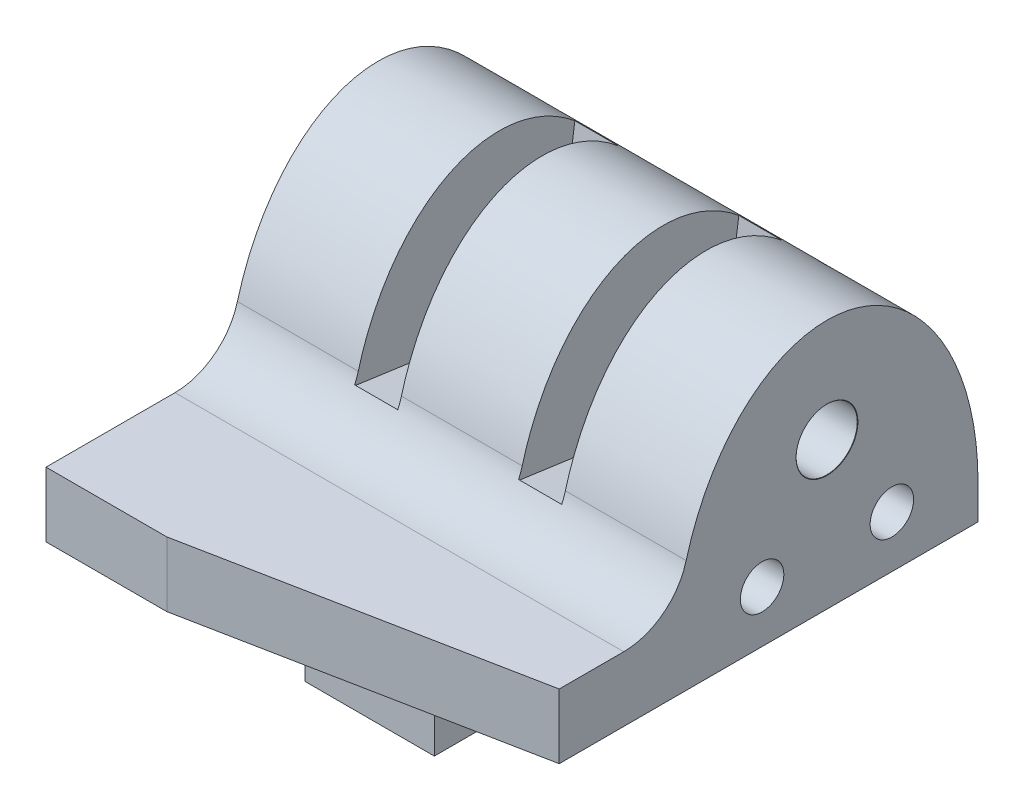
SolidWorks part; units mm, degrees
material "ABS"
ref_plane "Front Plane" through (0, 0, 0) normal (1, 0, 0) x (0, 1, 0)
ref_plane "Top Plane" through (0, 0, 0) normal (0, 0, 1) x (0, 1, 0)
ref_plane "Right Plane" through (0, 0, 0) normal (0, 1, 0) x (-1, 0, 0)
ref_plane "Plane1" through (8.89, 0, 0) normal (1, 0, 0) x (0, 1, 0)
sketch "Sketch1" plane through (0, 0, 0) normal (1, 0, 0) x (0, 1, 0)
  line L0 (0, 0) -> (0, 35.56)
  line L1 (0, 0) -> (-4.6261, 0) construction
  line L2 (0, 0) -> (2.54, 0)
  line L3 (0, 35.56) -> (4.7625, 35.56)
  line L4 (4.7625, 35.56) -> (4.7625, 26.0701)
  line L5 (2.54, 11.1125) -> (18.415, 11.1125) construction
  arc A0 (4.7625, 26.0701) -> (8.2778, 21.4738) centre (9.525, 26.0701) ccw
  ellipse E0 centre (2.54, 11.1125) end of major axis (-13.335, 11.1125) minor radius 11.1125 (2.54, 0) -> (8.2778, 21.4738) ccw
  point P12 (10.795, 11.1125)
  dimension "D3" = 22.225
  dimension "D4" = 4.7625
  dimension "D1" = 2.54
  dimension "D2" = 35.56
  dimension "D5" = 4.7625
  dimension "D6" = 31.75
  dimension "D7" = 7.62
extrude "Boss-Extrude1" add sketch "Sketch1" along normal blind 33.02
hole_wizard "M4 Clearance Hole1" positions "Sketch2" profile "Sketch3" hole size "M4" standard "ANSI Metric" end condition through all
sketch "Sketch2" plane through (33.02, 0, 0) normal (1, 0, 0) x (0, 0, -1)
  point P0 (-11.1125, 10.795)
sketch "Sketch3" plane through (33.02, 10.795, 11.1125) normal (0, 1, 0) x (0, 0, -1)
  line L0 (0, 0) -> (0, 33.02)
  line L1 (0, 33.02) -> (2.25, 33.02)
  line L2 (2.25, 33.02) -> (2.25, 0.021)
  line L3 (2.25, 0.021) -> (2.275, 0)
  line L5 (2.275, 0) -> (0, 0)
  line L6 (-2.25, 0.021) -> (-2.275, 0) construction
  line L11 (0, -6.35) -> (0, 107.95) construction
  dimension "Thru Hole Dia." = 4.5
  dimension "Thru Hole Depth" = 33.02
  dimension "Near C'Sink Dia." = 4.55
  dimension "Near C'Sink Angle" = 100
sketch "Sketch5" plane through (8.89, 0, 0) normal (-1, 0, 0) x (0, -1, 0)
  line L0 (0, 0) -> (0, 35.56) construction
  line L1 (0, 25.4) -> (9.525, 25.4)
  line L2 (0, 25.4) -> (0, 0)
  line L3 (0, 0) -> (9.525, 0)
  line L4 (9.525, 25.4) -> (9.525, 0)
  line L5 (4.7625, 19.05) -> (4.7625, 6.35)
  dimension "D1" = 12.7
  dimension "D2" = 4.7625
  dimension "D3" = 9.525
  dimension "D4" = 6.35
  dimension "D5" = 25.4
extrude "Boss-Extrude2" add sketch "Sketch5" against normal blind 9.525 contours L4 L1 L3 region at (8.89, -4.7625, 25.1287)
hole_wizard "#8 Clearance Hole1" positions "Sketch6" profile "Sketch7" hole size "#8" standard "ANSI Inch" end condition through all
sketch "Sketch6" plane through (0, 0, 0) normal (-1, 0, 0) x (0, 0, 1)
  point P0 (6.35, -4.7625)
  point P3 (19.05, -4.7625)
sketch "Sketch7" plane through (0, -4.7625, 6.35) normal (0, 1, 0) x (0, 0, 1)
  line L0 (0, 0) -> (0, 33.02)
  line L1 (0, 33.02) -> (2.2479, 33.02)
  line L2 (2.2479, 33.02) -> (2.2479, 0)
  line L5 (2.2479, 0) -> (0, 0)
  line L11 (0, -6.35) -> (0, 107.95) construction
  dimension "Thru Hole Dia." = 4.4958
  dimension "Thru Hole Depth" = 33.02
sketch "Sketch8" plane through (0, 4.7625, 0) normal (0, 1, 0) x (-1, 0, 0)
  line L0 (-33.02, 35.56) -> (-8.89, 35.56)
  line L1 (-8.89, 15.367) -> (-8.89, -15.367) construction
  line L2 (-33.02, 35.56) -> (0, 35.56) construction
  line L3 (-8.89, 35.56) -> (-33.02, 30.815)
  line L4 (-33.02, 26.0701) -> (-33.02, 35.56) construction
  line L5 (-33.02, 30.815) -> (-33.02, 35.56)
extrude "Cut-Extrude1" cut sketch "Sketch8" against normal through all both and the other way through all
sketch "Sketch9" plane through (8.89, 0, 0) normal (1, 0, 0) x (0, 1, 0)
  line L0 (7.4702, 21.6755) -> (5.416, 7.0592)
  line L1 (5.416, 7.0592) -> (16.2696, 5.5338)
  line L2 (5.416, 7.0592) -> (14.9798, 7.0592) construction
  line L5 (6.0788, 11.7753) -> (10.795, 11.1125) construction
  line L6 (10.1322, 6.3963) -> (10.795, 11.1125) construction
  line L7 (-9.525, 0) -> (93.5503, 0) construction
  line L8 (5.416, 7.0592) -> (49.4335, 0.8729) construction
  arc A0 (7.4702, 21.6755) -> (16.2696, 5.5338) centre (13.9484, 14.7377) cw
  ellipse E0 centre (2.54, 11.1125) end of major axis (-13.335, 11.1125) minor radius 11.1125 (2.54, 0) -> (8.2778, 21.4738) ccw construction
  dimension "D1" = 8
  dimension "D2" = 4.7625
  dimension "D3" = 4.7625
  dimension "D4" = 44.45
extrude "Cut-Extrude3" cut sketch "Sketch9" along normal blind 3.175
pattern_linear "LPattern1" count 2 spacing 12.065 along (1, 0, 0) of "Cut-Extrude3"
ref_plane "Plane3" through (27.94, 0, 0) normal (1, 0, 0) x (0, 0, -1)
sketch "Sketch12" plane through (27.94, 0, 0) normal (1, 0, 0) x (0, 0, -1)
  line L0 (0, 0) -> (-35.56, 0) construction
  line L1 (-3.5941, 0) -> (-9.0805, 0)
  line L2 (-3.5941, 0) -> (-3.5941, 3.81)
  line L3 (-3.5941, 3.81) -> (-9.0805, 3.81)
  line L4 (-9.0805, 0) -> (-9.0805, 3.81)
  line L5 (-11.1125, 2.54) -> (-11.1125, 18.415) construction
  line L6 (-18.6309, 0) -> (-13.1445, 0)
  line L7 (-18.6309, 0) -> (-18.6309, 3.81)
  line L8 (-18.6309, 3.81) -> (-13.1445, 3.81)
  line L9 (-13.1445, 0) -> (-13.1445, 3.81)
  line L10 (-15.8877, 6.9776) -> (-18.6309, 5.3938)
  line L11 (-18.6309, 5.3938) -> (-18.6309, 2.2262)
  line L12 (-18.6309, 2.2262) -> (-15.8877, 0.6424)
  line L13 (-15.8877, 0.6424) -> (-13.1445, 2.2262)
  line L14 (-13.1445, 2.2262) -> (-13.1445, 5.3938)
  line L15 (-13.1445, 5.3938) -> (-15.8877, 6.9776)
  line L16 (-6.3373, 6.9776) -> (-9.0805, 5.3938)
  line L17 (-9.0805, 5.3938) -> (-9.0805, 2.2262)
  line L18 (-9.0805, 2.2262) -> (-6.3373, 0.6424)
  line L19 (-6.3373, 0.6424) -> (-3.5941, 2.2262)
  line L20 (-3.5941, 2.2262) -> (-3.5941, 5.3938)
  line L21 (-3.5941, 5.3938) -> (-6.3373, 6.9776)
  circle A0 centre (-15.8877, 3.81) radius 2.7432 construction
  circle A1 centre (-6.3373, 3.81) radius 2.7432 construction
  dimension "D1" = 5.4864
  dimension "D2" = 5.4864
  dimension "D3" = 3.81
  dimension "D4" = 3.81
  dimension "D5" = 2.032
  dimension "D6" = 2.032
extrude "Cut-Extrude4" cut sketch "Sketch12" against normal blind 2.413 contours L13 L12 L7 L6 L9 | L14 L15 L10 L11 L8 | L20 L21 L16 L17 L3 | L18 L19 L2 L3 L4 | L19 L18 L4 L1 L2 | L12 L13 L9 L8 L7 region at (27.94, 0.0592, 6.3373) region at (27.94, 2.5782, 6.3373) region at (27.94, 5.0418, 6.3373) region at (27.94, 1.1131, 18.5717) region at (27.94, 2.5782, 15.8877) region at (27.94, 5.0418, 15.8877)
sketch "Sketch13" plane through (33.02, 0, 0) normal (1, 0, 0) x (0, 1, 0)
  line L0 (3.81, 18.6309) -> (3.81, 13.1445) construction
  circle A0 centre (3.81, 15.8877) radius 1.6
  circle A1 centre (3.81, 6.3373) radius 1.6
  dimension "D1" = 3.2
extrude "Cut-Extrude5" cut sketch "Sketch13" against normal blind 9.525
equation "\"D1@Sketch13\"=3.2mm"
